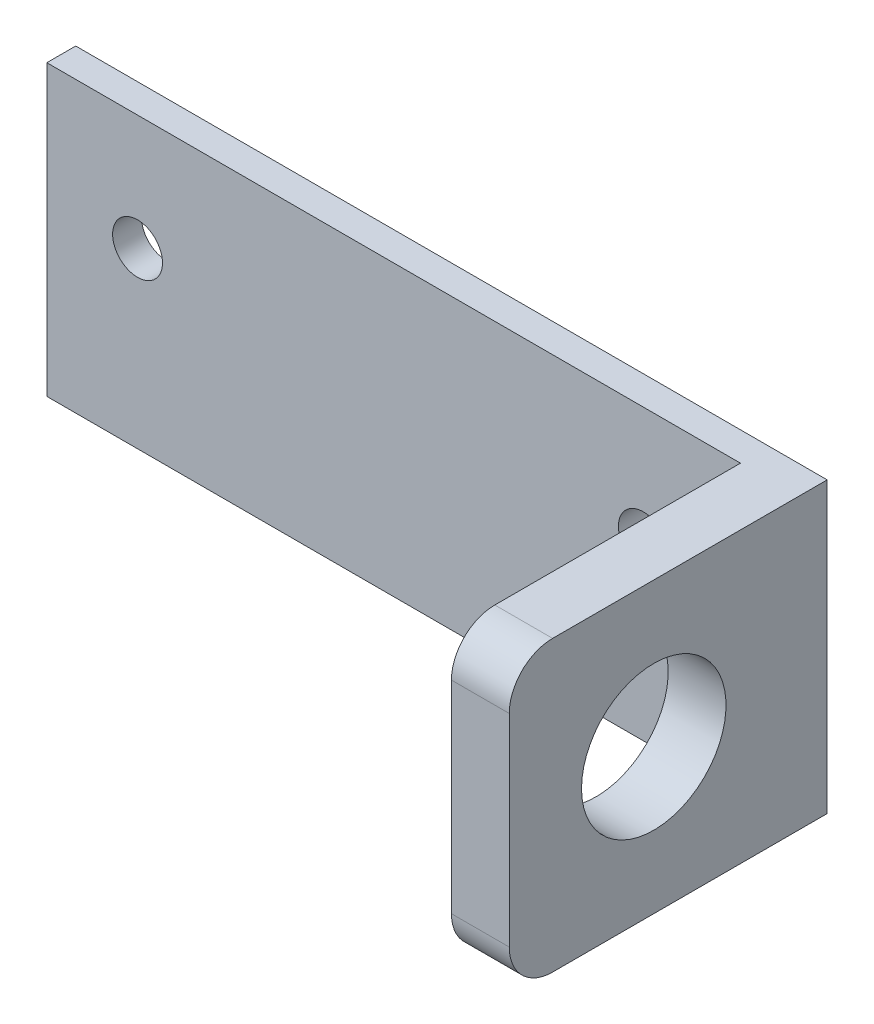
SolidWorks part; units mm, degrees
ref_plane "Front Plane" through (0, 0, 0) normal (0, 0, 1) x (1, 0, 0)
ref_plane "Top Plane" through (0, 0, 0) normal (0, 1, 0) x (1, 0, 0)
ref_plane "Right Plane" through (0, 0, 0) normal (1, 0, 0) x (0, 0, -1)
sketch "Sketch1" plane through (0, 0, 0) normal (0, 0, 1) x (1, 0, 0)
  line L1 (0, 0) -> (52, 0)
  line L2 (0, 0) -> (0, -20)
  line L3 (0, -20) -> (52, -20)
  line L4 (52, 0) -> (52, -20)
  dimension "D1" = 52
  dimension "D2" = 20
extrude "Boss-Extrude1" add sketch "Sketch1" along normal blind 2
ref_plane "Plane1" through (0, 0, 2) normal (0, 0, -1) x (-1, 0, 0)
sketch "Sketch2" plane through (0, 0, 2) normal (0, 0, -1) x (-1, 0, 0)
  line L1 (-48, 0) -> (-52, 0)
  line L2 (-48, 0) -> (-48, -20)
  line L3 (-48, -20) -> (-52, -20)
  line L4 (-52, 0) -> (-52, -20)
  dimension "D1" = 4
extrude "Boss-Extrude2" add sketch "Sketch2" against normal blind 20
sketch "Sketch3" plane through (48, 0, 0) normal (-1, 0, 0) x (0, 0, 1)
  line L0 (22, 0) -> (2, 0) construction
  line L1 (22, -20) -> (22, 0) construction
  circle A0 centre (12, -10) radius 5
  dimension "D1" = 10
  dimension "D2" = 10
  dimension "D3" = 10
extrude "Cut-Extrude1" cut sketch "Sketch3" against normal up to surface (4 mm away) up to face at (52, -10, 11)
fillet "Fillet1" radius 3 2 edges at (50, -20, 22) (50, 0, 22)
sketch "Sketch4" plane through (0, 0, 2) normal (0, 0, 1) x (1, 0, 0)
  line L0 (48, 0) -> (0, 0) construction
  circle A0 centre (41.2777, -8) radius 1.725
  circle A1 centre (6.2777, -8) radius 1.725
  dimension "D1" = 35
  dimension "D2" = 8
  dimension "D3" = 8
extrude "Cut-Extrude2" cut sketch "Sketch4" against normal up to surface (2 mm away) up to face at (26, -10, 0)
